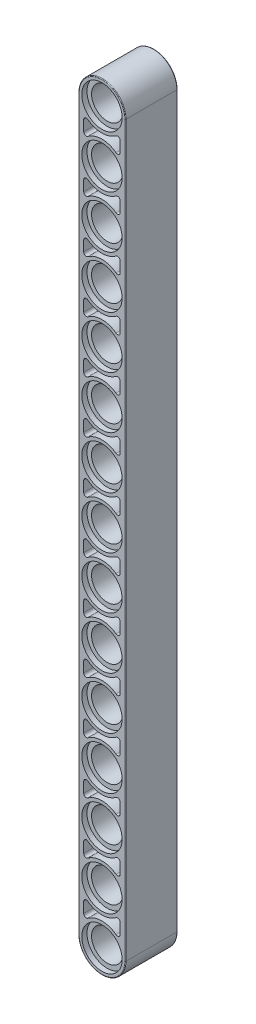
SolidWorks part; units mm, degrees
ref_plane "Front Plane" through (0, 0, 0) normal (0, 0, 1) x (1, 0, 0)
ref_plane "Top Plane" through (0, 0, 0) normal (0, 1, 0) x (1, 0, 0)
ref_plane "Right Plane" through (0, 0, 0) normal (1, 0, 0) x (0, 0, -1)
ref_plane "Plane1" through (0, 0, 4) normal (0, 0, 1) x (1, 0, 0)
sketch "Sketch1" plane through (0, 0, 4) normal (0, 0, 1) x (1, 0, 0)
  line L0 (3.6, -56) -> (3.6, 56)
  line L1 (-3.6, 56) -> (-3.6, -56)
  line L2 (3.6, 0) -> (-3.6, 0) construction
  arc A0 (3.6, 56) -> (-3.6, 56) centre (0, 56) ccw
  arc A1 (-3.6, -56) -> (3.6, -56) centre (0, -56) ccw
  point P6 (0, 0)
  dimension "D2" = 3.6
  dimension "D1" = 112
extrude "Boss-Extrude1" add sketch "Sketch1" against normal blind 8
sketch "Sketch2" plane through (0, 0, 4) normal (0, 0, 1) x (1, 0, 0)
  line L0 (-2.8, -27.2) -> (-2.8, -28.8)
  line L1 (2.8, -28.8) -> (2.8, -27.2)
  arc A0 (2.16, -26.88) -> (-2.16, -26.88) centre (0, -24) cw
  arc A1 (-2.16, -26.88) -> (-2.8, -27.2) centre (-2.4, -27.2) ccw
  arc A2 (-2.8, -28.8) -> (-2.16, -29.12) centre (-2.4, -28.8) ccw
  arc A3 (-2.16, -29.12) -> (2.16, -29.12) centre (0, -32) cw
  arc A4 (2.16, -29.12) -> (2.8, -28.8) centre (2.4, -28.8) ccw
  arc A5 (2.8, -27.2) -> (2.16, -26.88) centre (2.4, -27.2) ccw
extrude "Cut-Extrude1" cut sketch "Sketch2" against normal blind 3.1
sketch "Sketch3" plane through (0, 0, 4) normal (0, 0, 1) x (1, 0, 0)
  line L0 (-2.8, -11.2) -> (-2.8, -12.8)
  line L1 (2.8, -12.8) -> (2.8, -11.2)
  arc A0 (2.16, -10.88) -> (-2.16, -10.88) centre (0, -8) cw
  arc A1 (-2.16, -10.88) -> (-2.8, -11.2) centre (-2.4, -11.2) ccw
  arc A2 (-2.8, -12.8) -> (-2.16, -13.12) centre (-2.4, -12.8) ccw
  arc A3 (-2.16, -13.12) -> (2.16, -13.12) centre (0, -16) cw
  arc A4 (2.16, -13.12) -> (2.8, -12.8) centre (2.4, -12.8) ccw
  arc A5 (2.8, -11.2) -> (2.16, -10.88) centre (2.4, -11.2) ccw
extrude "Cut-Extrude2" cut sketch "Sketch3" against normal blind 3.1
sketch "Sketch4" plane through (0, 0, 4) normal (0, 0, 1) x (1, 0, 0)
  line L0 (-2.8, 4.8) -> (-2.8, 3.2)
  line L1 (2.8, 3.2) -> (2.8, 4.8)
  arc A0 (2.16, 5.12) -> (-2.16, 5.12) centre (0, 8) cw
  arc A1 (-2.16, 5.12) -> (-2.8, 4.8) centre (-2.4, 4.8) ccw
  arc A2 (-2.8, 3.2) -> (-2.16, 2.88) centre (-2.4, 3.2) ccw
  arc A3 (-2.16, 2.88) -> (2.16, 2.88) centre (0, 0) cw
  arc A4 (2.16, 2.88) -> (2.8, 3.2) centre (2.4, 3.2) ccw
  arc A5 (2.8, 4.8) -> (2.16, 5.12) centre (2.4, 4.8) ccw
extrude "Cut-Extrude3" cut sketch "Sketch4" against normal blind 3.1
sketch "Sketch5" plane through (0, 0, 4) normal (0, 0, 1) x (1, 0, 0)
  line L0 (-2.8, 20.8) -> (-2.8, 19.2)
  line L1 (2.8, 19.2) -> (2.8, 20.8)
  arc A0 (2.16, 21.12) -> (-2.16, 21.12) centre (0, 24) cw
  arc A1 (-2.16, 21.12) -> (-2.8, 20.8) centre (-2.4, 20.8) ccw
  arc A2 (-2.8, 19.2) -> (-2.16, 18.88) centre (-2.4, 19.2) ccw
  arc A3 (-2.16, 18.88) -> (2.16, 18.88) centre (0, 16) cw
  arc A4 (2.16, 18.88) -> (2.8, 19.2) centre (2.4, 19.2) ccw
  arc A5 (2.8, 20.8) -> (2.16, 21.12) centre (2.4, 20.8) ccw
extrude "Cut-Extrude4" cut sketch "Sketch5" against normal blind 3.1
sketch "Sketch6" plane through (0, 0, 4) normal (0, 0, 1) x (1, 0, 0)
  line L0 (2.8, 27.2) -> (2.8, 28.8)
  line L1 (-2.8, 28.8) -> (-2.8, 27.2)
  arc A0 (2.8, 28.8) -> (2.16, 29.12) centre (2.4, 28.8) ccw
  arc A1 (2.16, 29.12) -> (-2.16, 29.12) centre (0, 32) cw
  arc A2 (-2.16, 29.12) -> (-2.8, 28.8) centre (-2.4, 28.8) ccw
  arc A3 (-2.8, 27.2) -> (-2.16, 26.88) centre (-2.4, 27.2) ccw
  arc A4 (-2.16, 26.88) -> (2.16, 26.88) centre (0, 24) cw
  arc A5 (2.16, 26.88) -> (2.8, 27.2) centre (2.4, 27.2) ccw
extrude "Cut-Extrude5" cut sketch "Sketch6" against normal blind 3.1
sketch "Sketch7" plane through (0, 0, 4) normal (0, 0, 1) x (1, 0, 0)
  line L0 (-2.8, 12.8) -> (-2.8, 11.2)
  line L1 (2.8, 11.2) -> (2.8, 12.8)
  arc A0 (2.16, 13.12) -> (-2.16, 13.12) centre (0, 16) cw
  arc A1 (-2.16, 13.12) -> (-2.8, 12.8) centre (-2.4, 12.8) ccw
  arc A2 (-2.8, 11.2) -> (-2.16, 10.88) centre (-2.4, 11.2) ccw
  arc A3 (-2.16, 10.88) -> (2.16, 10.88) centre (0, 8) cw
  arc A4 (2.16, 10.88) -> (2.8, 11.2) centre (2.4, 11.2) ccw
  arc A5 (2.8, 12.8) -> (2.16, 13.12) centre (2.4, 12.8) ccw
extrude "Cut-Extrude6" cut sketch "Sketch7" against normal blind 3.1
sketch "Sketch8" plane through (0, 0, 4) normal (0, 0, 1) x (1, 0, 0)
  line L0 (-2.8, -3.2) -> (-2.8, -4.8)
  line L1 (2.8, -4.8) -> (2.8, -3.2)
  arc A0 (2.16, -2.88) -> (-2.16, -2.88) centre (0, 0) cw
  arc A1 (-2.16, -2.88) -> (-2.8, -3.2) centre (-2.4, -3.2) ccw
  arc A2 (-2.8, -4.8) -> (-2.16, -5.12) centre (-2.4, -4.8) ccw
  arc A3 (-2.16, -5.12) -> (2.16, -5.12) centre (0, -8) cw
  arc A4 (2.16, -5.12) -> (2.8, -4.8) centre (2.4, -4.8) ccw
  arc A5 (2.8, -3.2) -> (2.16, -2.88) centre (2.4, -3.2) ccw
extrude "Cut-Extrude7" cut sketch "Sketch8" against normal blind 3.1
sketch "Sketch9" plane through (0, 0, 4) normal (0, 0, 1) x (1, 0, 0)
  line L0 (-2.8, -19.2) -> (-2.8, -20.8)
  line L1 (2.8, -20.8) -> (2.8, -19.2)
  arc A0 (2.16, -18.88) -> (-2.16, -18.88) centre (0, -16) cw
  arc A1 (-2.16, -18.88) -> (-2.8, -19.2) centre (-2.4, -19.2) ccw
  arc A2 (-2.8, -20.8) -> (-2.16, -21.12) centre (-2.4, -20.8) ccw
  arc A3 (-2.16, -21.12) -> (2.16, -21.12) centre (0, -24) cw
  arc A4 (2.16, -21.12) -> (2.8, -20.8) centre (2.4, -20.8) ccw
  arc A5 (2.8, -19.2) -> (2.16, -18.88) centre (2.4, -19.2) ccw
extrude "Cut-Extrude8" cut sketch "Sketch9" against normal blind 3.1
sketch "Sketch10" plane through (0, 0, -4) normal (0, 0, -1) x (-1, 0, 0)
  line L0 (-2.8, -27.2) -> (-2.8, -28.8)
  line L1 (2.8, -28.8) -> (2.8, -27.2)
  arc A0 (-2.8, -28.8) -> (-2.16, -29.12) centre (-2.4, -28.8) ccw
  arc A1 (-2.16, -29.12) -> (2.16, -29.12) centre (0, -32) cw
  arc A2 (2.16, -29.12) -> (2.8, -28.8) centre (2.4, -28.8) ccw
  arc A3 (2.8, -27.2) -> (2.16, -26.88) centre (2.4, -27.2) ccw
  arc A4 (2.16, -26.88) -> (-2.16, -26.88) centre (0, -24) cw
  arc A5 (-2.16, -26.88) -> (-2.8, -27.2) centre (-2.4, -27.2) ccw
extrude "Cut-Extrude9" cut sketch "Sketch10" against normal blind 3.1
sketch "Sketch11" plane through (0, 0, -4) normal (0, 0, -1) x (-1, 0, 0)
  line L0 (-2.8, -19.2) -> (-2.8, -20.8)
  line L1 (2.8, -20.8) -> (2.8, -19.2)
  arc A0 (-2.8, -20.8) -> (-2.16, -21.12) centre (-2.4, -20.8) ccw
  arc A1 (-2.16, -21.12) -> (2.16, -21.12) centre (0, -24) cw
  arc A2 (2.16, -21.12) -> (2.8, -20.8) centre (2.4, -20.8) ccw
  arc A3 (2.8, -19.2) -> (2.16, -18.88) centre (2.4, -19.2) ccw
  arc A4 (2.16, -18.88) -> (-2.16, -18.88) centre (0, -16) cw
  arc A5 (-2.16, -18.88) -> (-2.8, -19.2) centre (-2.4, -19.2) ccw
extrude "Cut-Extrude10" cut sketch "Sketch11" against normal blind 3.1
sketch "Sketch12" plane through (0, 0, -4) normal (0, 0, -1) x (-1, 0, 0)
  line L0 (-2.8, -11.2) -> (-2.8, -12.8)
  line L1 (2.8, -12.8) -> (2.8, -11.2)
  arc A0 (-2.8, -12.8) -> (-2.16, -13.12) centre (-2.4, -12.8) ccw
  arc A1 (-2.16, -13.12) -> (2.16, -13.12) centre (0, -16) cw
  arc A2 (2.16, -13.12) -> (2.8, -12.8) centre (2.4, -12.8) ccw
  arc A3 (2.8, -11.2) -> (2.16, -10.88) centre (2.4, -11.2) ccw
  arc A4 (2.16, -10.88) -> (-2.16, -10.88) centre (0, -8) cw
  arc A5 (-2.16, -10.88) -> (-2.8, -11.2) centre (-2.4, -11.2) ccw
extrude "Cut-Extrude11" cut sketch "Sketch12" against normal blind 3.1
sketch "Sketch13" plane through (0, 0, -4) normal (0, 0, -1) x (-1, 0, 0)
  line L0 (-2.8, -3.2) -> (-2.8, -4.8)
  line L1 (2.8, -4.8) -> (2.8, -3.2)
  arc A0 (-2.8, -4.8) -> (-2.16, -5.12) centre (-2.4, -4.8) ccw
  arc A1 (-2.16, -5.12) -> (2.16, -5.12) centre (0, -8) cw
  arc A2 (2.16, -5.12) -> (2.8, -4.8) centre (2.4, -4.8) ccw
  arc A3 (2.8, -3.2) -> (2.16, -2.88) centre (2.4, -3.2) ccw
  arc A4 (2.16, -2.88) -> (-2.16, -2.88) centre (0, 0) cw
  arc A5 (-2.16, -2.88) -> (-2.8, -3.2) centre (-2.4, -3.2) ccw
extrude "Cut-Extrude12" cut sketch "Sketch13" against normal blind 3.1
sketch "Sketch14" plane through (0, 0, -4) normal (0, 0, -1) x (-1, 0, 0)
  line L0 (-2.8, 4.8) -> (-2.8, 3.2)
  line L1 (2.8, 3.2) -> (2.8, 4.8)
  arc A0 (-2.8, 3.2) -> (-2.16, 2.88) centre (-2.4, 3.2) ccw
  arc A1 (-2.16, 2.88) -> (2.16, 2.88) centre (0, 0) cw
  arc A2 (2.16, 2.88) -> (2.8, 3.2) centre (2.4, 3.2) ccw
  arc A3 (2.8, 4.8) -> (2.16, 5.12) centre (2.4, 4.8) ccw
  arc A4 (2.16, 5.12) -> (-2.16, 5.12) centre (0, 8) cw
  arc A5 (-2.16, 5.12) -> (-2.8, 4.8) centre (-2.4, 4.8) ccw
extrude "Cut-Extrude13" cut sketch "Sketch14" against normal blind 3.1
sketch "Sketch15" plane through (0, 0, -4) normal (0, 0, -1) x (-1, 0, 0)
  line L0 (-2.8, 12.8) -> (-2.8, 11.2)
  line L1 (2.8, 11.2) -> (2.8, 12.8)
  arc A0 (-2.8, 11.2) -> (-2.16, 10.88) centre (-2.4, 11.2) ccw
  arc A1 (-2.16, 10.88) -> (2.16, 10.88) centre (0, 8) cw
  arc A2 (2.16, 10.88) -> (2.8, 11.2) centre (2.4, 11.2) ccw
  arc A3 (2.8, 12.8) -> (2.16, 13.12) centre (2.4, 12.8) ccw
  arc A4 (2.16, 13.12) -> (-2.16, 13.12) centre (0, 16) cw
  arc A5 (-2.16, 13.12) -> (-2.8, 12.8) centre (-2.4, 12.8) ccw
extrude "Cut-Extrude14" cut sketch "Sketch15" against normal blind 3.1
sketch "Sketch16" plane through (0, 0, -4) normal (0, 0, -1) x (-1, 0, 0)
  line L0 (-2.8, 20.8) -> (-2.8, 19.2)
  line L1 (2.8, 19.2) -> (2.8, 20.8)
  arc A0 (-2.8, 19.2) -> (-2.16, 18.88) centre (-2.4, 19.2) ccw
  arc A1 (-2.16, 18.88) -> (2.16, 18.88) centre (0, 16) cw
  arc A2 (2.16, 18.88) -> (2.8, 19.2) centre (2.4, 19.2) ccw
  arc A3 (2.8, 20.8) -> (2.16, 21.12) centre (2.4, 20.8) ccw
  arc A4 (2.16, 21.12) -> (-2.16, 21.12) centre (0, 24) cw
  arc A5 (-2.16, 21.12) -> (-2.8, 20.8) centre (-2.4, 20.8) ccw
extrude "Cut-Extrude15" cut sketch "Sketch16" against normal blind 3.1
sketch "Sketch17" plane through (0, 0, -4) normal (0, 0, -1) x (-1, 0, 0)
  line L0 (-2.8, 28.8) -> (-2.8, 27.2)
  line L1 (2.8, 27.2) -> (2.8, 28.8)
  arc A0 (-2.8, 27.2) -> (-2.16, 26.88) centre (-2.4, 27.2) ccw
  arc A1 (-2.16, 26.88) -> (2.16, 26.88) centre (0, 24) cw
  arc A2 (2.16, 26.88) -> (2.8, 27.2) centre (2.4, 27.2) ccw
  arc A3 (2.8, 28.8) -> (2.16, 29.12) centre (2.4, 28.8) ccw
  arc A4 (2.16, 29.12) -> (-2.16, 29.12) centre (0, 32) cw
  arc A5 (-2.16, 29.12) -> (-2.8, 28.8) centre (-2.4, 28.8) ccw
extrude "Cut-Extrude16" cut sketch "Sketch17" against normal blind 3.1
ref_plane "Plane2" through (0, -32, 0) normal (0, 1, 0) x (1, 0, 0)
sketch "Sketch18" plane through (0, -32, 0) normal (0, 1, 0) x (1, 0, 0)
  line L0 (3.1, 4) -> (0, 4)
  line L1 (0, 4) -> (0, -4)
  line L2 (0, -4) -> (3.1, -4)
  line L3 (3.1, -4) -> (3.1, -3.2)
  line L4 (3.1, -3.2) -> (2.4, -3.2)
  line L5 (2.4, -3.2) -> (2.4, 3.2)
  line L6 (2.4, 3.2) -> (3.1, 3.2)
  line L7 (3.1, 3.2) -> (3.1, 4)
  line L8 (0, 4) -> (0, -4) construction
revolve "Cut-Revolve1" cut sketch "Sketch18" angle 360 about L8 reverse direction yes
ref_plane "Plane3" through (0, -24, 0) normal (0, 1, 0) x (1, 0, 0)
sketch "Sketch19" plane through (0, -24, 0) normal (0, 1, 0) x (1, 0, 0)
  line L0 (3.1, 4) -> (0, 4)
  line L1 (0, 4) -> (0, -4)
  line L2 (0, -4) -> (3.1, -4)
  line L3 (3.1, -4) -> (3.1, -3.2)
  line L4 (3.1, -3.2) -> (2.4, -3.2)
  line L5 (2.4, -3.2) -> (2.4, 3.2)
  line L6 (2.4, 3.2) -> (3.1, 3.2)
  line L7 (3.1, 3.2) -> (3.1, 4)
  line L8 (0, 4) -> (0, -4) construction
revolve "Cut-Revolve2" cut sketch "Sketch19" angle 360 about L8 reverse direction yes
ref_plane "Plane4" through (0, -16, 0) normal (0, 1, 0) x (1, 0, 0)
sketch "Sketch20" plane through (0, -16, 0) normal (0, 1, 0) x (1, 0, 0)
  line L0 (3.1, 4) -> (0, 4)
  line L1 (0, 4) -> (0, -4)
  line L2 (0, -4) -> (3.1, -4)
  line L3 (3.1, -4) -> (3.1, -3.2)
  line L4 (3.1, -3.2) -> (2.4, -3.2)
  line L5 (2.4, -3.2) -> (2.4, 3.2)
  line L6 (2.4, 3.2) -> (3.1, 3.2)
  line L7 (3.1, 3.2) -> (3.1, 4)
  line L8 (0, 4) -> (0, -4) construction
revolve "Cut-Revolve3" cut sketch "Sketch20" angle 360 about L8 reverse direction yes
ref_plane "Plane5" through (0, -8, 0) normal (0, 1, 0) x (1, 0, 0)
sketch "Sketch21" plane through (0, -8, 0) normal (0, 1, 0) x (1, 0, 0)
  line L0 (3.1, 4) -> (0, 4)
  line L1 (0, 4) -> (0, -4)
  line L2 (0, -4) -> (3.1, -4)
  line L3 (3.1, -4) -> (3.1, -3.2)
  line L4 (3.1, -3.2) -> (2.4, -3.2)
  line L5 (2.4, -3.2) -> (2.4, 3.2)
  line L6 (2.4, 3.2) -> (3.1, 3.2)
  line L7 (3.1, 3.2) -> (3.1, 4)
  line L8 (0, 4) -> (0, -4) construction
revolve "Cut-Revolve4" cut sketch "Sketch21" angle 360 about L8 reverse direction yes
sketch "Sketch22" plane through (0, 0, 0) normal (0, 1, 0) x (1, 0, 0)
  line L0 (3.1, 4) -> (0, 4)
  line L1 (0, 4) -> (0, -4)
  line L2 (0, -4) -> (3.1, -4)
  line L3 (3.1, -4) -> (3.1, -3.2)
  line L4 (3.1, -3.2) -> (2.4, -3.2)
  line L5 (2.4, -3.2) -> (2.4, 3.2)
  line L6 (2.4, 3.2) -> (3.1, 3.2)
  line L7 (3.1, 3.2) -> (3.1, 4)
  line L8 (0, 4) -> (0, -4) construction
revolve "Cut-Revolve5" cut sketch "Sketch22" angle 360 about L8 reverse direction yes
ref_plane "Plane6" through (0, 8, 0) normal (0, 1, 0) x (1, 0, 0)
sketch "Sketch23" plane through (0, 8, 0) normal (0, 1, 0) x (1, 0, 0)
  line L0 (3.1, 4) -> (0, 4)
  line L1 (0, 4) -> (0, -4)
  line L2 (0, -4) -> (3.1, -4)
  line L3 (3.1, -4) -> (3.1, -3.2)
  line L4 (3.1, -3.2) -> (2.4, -3.2)
  line L5 (2.4, -3.2) -> (2.4, 3.2)
  line L6 (2.4, 3.2) -> (3.1, 3.2)
  line L7 (3.1, 3.2) -> (3.1, 4)
  line L8 (0, 4) -> (0, -4) construction
revolve "Cut-Revolve6" cut sketch "Sketch23" angle 360 about L8 reverse direction yes
ref_plane "Plane7" through (0, 16, 0) normal (0, 1, 0) x (1, 0, 0)
sketch "Sketch24" plane through (0, 16, 0) normal (0, 1, 0) x (1, 0, 0)
  line L0 (3.1, 4) -> (0, 4)
  line L1 (0, 4) -> (0, -4)
  line L2 (0, -4) -> (3.1, -4)
  line L3 (3.1, -4) -> (3.1, -3.2)
  line L4 (3.1, -3.2) -> (2.4, -3.2)
  line L5 (2.4, -3.2) -> (2.4, 3.2)
  line L6 (2.4, 3.2) -> (3.1, 3.2)
  line L7 (3.1, 3.2) -> (3.1, 4)
  line L8 (0, 4) -> (0, -4) construction
revolve "Cut-Revolve7" cut sketch "Sketch24" angle 360 about L8 reverse direction yes
ref_plane "Plane8" through (0, 24, 0) normal (0, 1, 0) x (1, 0, 0)
sketch "Sketch25" plane through (0, 24, 0) normal (0, 1, 0) x (1, 0, 0)
  line L0 (3.1, 4) -> (0, 4)
  line L1 (0, 4) -> (0, -4)
  line L2 (0, -4) -> (3.1, -4)
  line L3 (3.1, -4) -> (3.1, -3.2)
  line L4 (3.1, -3.2) -> (2.4, -3.2)
  line L5 (2.4, -3.2) -> (2.4, 3.2)
  line L6 (2.4, 3.2) -> (3.1, 3.2)
  line L7 (3.1, 3.2) -> (3.1, 4)
  line L8 (0, 4) -> (0, -4) construction
revolve "Cut-Revolve8" cut sketch "Sketch25" angle 360 about L8 reverse direction yes
ref_plane "Plane9" through (0, 32, 0) normal (0, 1, 0) x (1, 0, 0)
sketch "Sketch26" plane through (0, 32, 0) normal (0, 1, 0) x (1, 0, 0)
  line L0 (3.1, 4) -> (0, 4)
  line L1 (0, 4) -> (0, -4)
  line L2 (0, -4) -> (3.1, -4)
  line L3 (3.1, -4) -> (3.1, -3.2)
  line L4 (3.1, -3.2) -> (2.4, -3.2)
  line L5 (2.4, -3.2) -> (2.4, 3.2)
  line L6 (2.4, 3.2) -> (3.1, 3.2)
  line L7 (3.1, 3.2) -> (3.1, 4)
  line L8 (0, 4) -> (0, -4) construction
revolve "Cut-Revolve9" cut sketch "Sketch26" angle 360 about L8 reverse direction yes
fillet "Fillet1" radius 0.1 8 edges at (0, 59.6, -4) (3.6, 0, -4) (-3.6, 0, -4) (0, -59.6, -4) (-3.6, 0, 4) (0, 59.6, 4) (0, -59.6, 4) (3.6, 0, 4) tangent propagation no
pattern_linear "LPattern1" count 4 spacing 8 along (0, 1, 0) count 12 spacing 8 along (0, -1, 0) of "Cut-Revolve9"
pattern_linear "LPattern2" count 9 spacing 8 along (0, -1, 0) count 6 spacing 8 along (0, 1, 0) of "Cut-Extrude6"
mirror "Mirror1" about plane through (0, 0, 0) normal (0, 0, 1) of "LPattern2"
